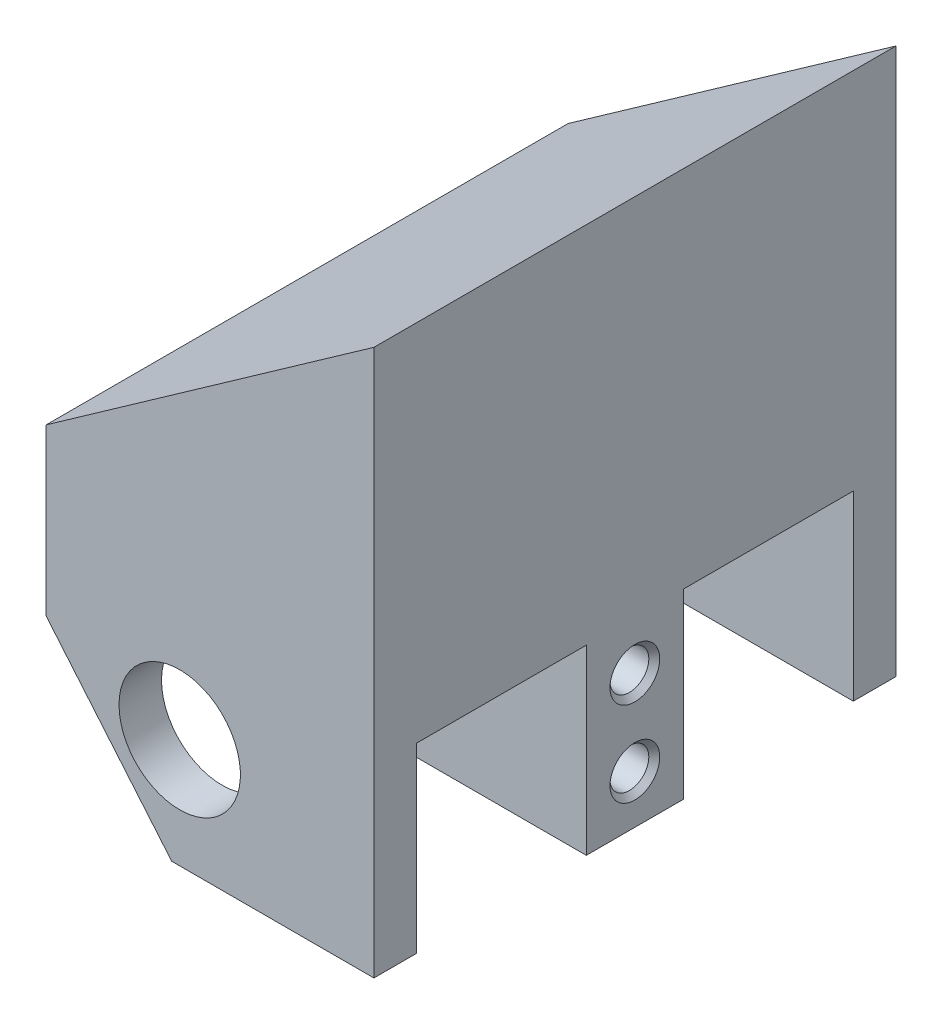
SolidWorks part; units mm, degrees
ref_plane "Front Plane" through (0, 0, 0) normal (0, 0, 1) x (1, 0, 0)
ref_plane "Top Plane" through (0, 0, 0) normal (0, 1, 0) x (1, 0, 0)
ref_plane "Right Plane" through (0, 0, 0) normal (1, 0, 0) x (0, 0, -1)
sketch "Sketch1" plane through (0, 0, 0) normal (0, 0, 1) x (1, 0, 0)
  line L0 (-7.2764, -10.5186) -> (2.2236, -16.0034)
  line L1 (2.2236, -16.0034) -> (6.2236, -16.0034)
  line L2 (-7.2764, -10.5186) -> (-7.2764, -0.5186)
  line L4 (6.2236, -16.0034) -> (6.2236, 8.9966)
  line L5 (-7.2764, -10.5186) -> (6.2236, 8.9966) construction
  line L6 (-1.4071, 3.6183) -> (6.2236, -16.0034) construction
  line L7 (-7.2764, -0.5186) -> (6.2236, 8.9966)
  point P0 (0, 0)
  point P6 (-8.0456, -11.0255)
  point P11 (1.9331, -14.0255)
  dimension "D1" = 13.5
  dimension "D2" = 25
  dimension "D3" = 4
  dimension "D4" = 30
  dimension "D5" = 10
extrude "Boss-Extrude1" add sketch "Sketch1" along normal blind 21.5
sketch "Sketch2" plane through (0, 0, 0) normal (0, 0, -1) x (-1, 0, 0)
  line L0 (7.2764, -0.5186) -> (7.2764, -10.5186) construction
  line L1 (-6.2236, -16.0034) -> (-6.2236, 8.9966) construction
  line L3 (-2.2236, -16.0034) -> (-6.2236, -16.0034) construction
  circle A0 centre (1.7764, -9.0034) radius 2.5
  circle A1 centre (4.2764, -3.0034) radius 2.5
  point P4 (0, 0)
  point P5 (0, 0)
  point P10 (0, 0)
  dimension "D1" = 5
  dimension "D2" = 5
  dimension "D3" = 5.5
  dimension "D4" = 10.5
  dimension "D5" = 7
  dimension "D6" = 13
extrude "Cut-Extrude1" cut sketch "Sketch2" against normal through all contours A0 region at (-1.7764, -9.0034, 0)
extrude "Cut-Extrude2" cut sketch "Sketch2<3>" against normal blind 11 contours A1 region at (-4.2764, -3.0034, 0)
sketch "Sketch2<3>" plane through (0, 0, 0) normal (0, 0, -1) x (-1, 0, 0) same geometry as "Sketch2"
sketch "Sketch5" plane through (0, 0, 0) normal (0, 0, -1) x (-1, 0, 0)
  line L0 (-6.2236, -13.5034) -> (2.1066, -13.5034)
  line L1 (-6.2236, -16.0034) -> (-6.2236, 8.9966) construction
  line L2 (7.2764, -10.5186) -> (-2.2236, -16.0034) construction
  line L3 (2.1066, -13.5034) -> (-2.2236, -16.0034)
  line L4 (-2.2236, -16.0034) -> (-6.2236, -16.0034)
  line L5 (-6.2236, -16.0034) -> (-6.2236, -13.5034)
  dimension "D1" = 2.5
extrude "Cut-Extrude3" cut sketch "Sketch5" against normal through all
sketch "Sketch6" plane through (0, 0, 0) normal (0, 0, -1) x (-1, 0, 0)
  line L0 (2.1066, -13.5034) -> (7.2764, -7.3422)
  line L1 (7.2764, -0.5186) -> (7.2764, -10.5186) construction
  line L2 (7.2764, -7.3422) -> (7.2764, -10.5186)
  line L3 (7.2764, -10.5186) -> (2.1066, -13.5034)
  dimension "D1" = 20
extrude "Cut-Extrude4" cut sketch "Sketch6" against normal through all
sketch "Sketch7" plane through (6.2236, 0, 0) normal (1, 0, 0) x (0, 0, -1)
  line L0 (-10.75, 8.9966) -> (-10.75, -14.2492) construction
  line L1 (-21.5, 8.9966) -> (0, 8.9966) construction
  line L2 (-21.5, -13.5034) -> (0, -13.5034) construction
  line L3 (-19.75, -13.5034) -> (-12.75, -13.5034)
  line L4 (-19.75, -13.5034) -> (-19.75, -6.0034)
  line L5 (-19.75, -6.0034) -> (-12.75, -6.0034)
  line L6 (-12.75, -13.5034) -> (-12.75, -6.0034)
  line L7 (-1.75, -6.0034) -> (-8.75, -6.0034)
  line L8 (-8.75, -13.5034) -> (-8.75, -6.0034)
  line L9 (-1.75, -13.5034) -> (-8.75, -13.5034)
  line L10 (-1.75, -13.5034) -> (-1.75, -6.0034)
  line M7 (-21.5, -13.5034) -> (0, -13.5034)
  dimension "D1" = 7.5
  dimension "D2" = 7
  dimension "D3" = 2
extrude "Cut-Extrude5" cut sketch "Sketch7" against normal through all contours L6 L5 L4 M7 | L10 L7 L8 M7 region at (6.2236, -9.7534, 16.25) region at (6.2236, -9.7534, 5.25)
hole_wizard "M2x0.4 Tapped Hole1" positions "Sketch9" profile "Sketch10" tap size "M2x0.4" standard "ANSI Metric"
sketch "Sketch9" plane through (6.2236, 0, 0) normal (1, 0, 0) x (0, 0, -1)
  line L0 (-12.75, -13.5034) -> (-8.75, -13.5034) construction
  line L1 (-12.75, -13.5034) -> (-12.75, -6.0034) construction
  point P0 (-10.75, -8.0034)
  point P2 (-10.75, -11.5034)
  dimension "D1" = 2
  dimension "D2" = 3.5
  dimension "D3" = 2
  dimension "D4" = 2
cosmetic thread "Hole Thread1" parameters "D2"=2
cosmetic thread "Hole Thread2" parameters "D2"=2
sketch "Sketch10" plane through (6.2236, -8.0034, 10.75) normal (0, 1, 0) x (0, 0, -1)
  line L0 (0, 0) -> (0, 5.4807)
  line L1 (0, 5.4807) -> (0.8, 5)
  line L2 (0.8, 5) -> (0.8, 0.225)
  line L3 (0.8, 0.225) -> (1.025, 0)
  line L5 (1.025, 0) -> (0, 0)
  line L6 (-0.8, 0.225) -> (-1.025, 0) construction
  line L10 (0, 5.4807) -> (-0.8, 5) construction
  line L11 (0, -6.35) -> (0, 107.95) construction
  dimension "Tap Drill Dia." = 1.6
  dimension "Tap Drill Depth" = 5
  dimension "Near C'Sink Dia." = 2.05
  dimension "Near C'Sink Angle" = 90
  dimension "Drill Angle" = 118
